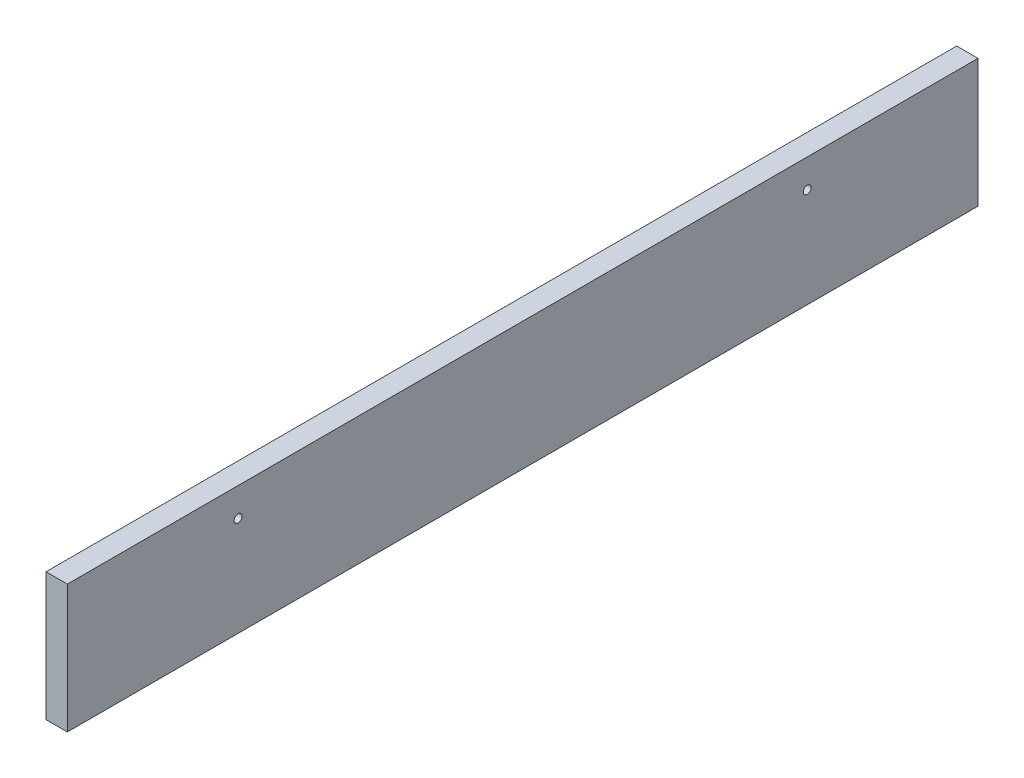
SolidWorks part; units mm, degrees
ref_plane "Front Plane" through (0, 0, 0) normal (0, 0, 1) x (1, 0, 0)
ref_plane "Top Plane" through (0, 0, 0) normal (0, 1, 0) x (1, 0, 0)
ref_plane "Right Plane" through (0, 0, 0) normal (1, 0, 0) x (0, 0, -1)
sketch "Sketch1" plane through (0, 0, 0) normal (0, 0, 1) x (1, 0, 0)
  line L1 (-6.3285, 7.7245) -> (12.7215, 7.7245)
  line L2 (-6.3285, 7.7245) -> (-6.3285, -106.5755)
  line L3 (-6.3285, -106.5755) -> (12.7215, -106.5755)
  line L4 (12.7215, 7.7245) -> (12.7215, -106.5755)
  dimension "D1" = 19.05
  dimension "D2" = 114.3
extrude "Boss-Extrude1" add sketch "Sketch1" along normal blind 812.8
ref_plane "Plane1" through (0, 0, 406.4) normal (0, 0, 1) x (1, 0, 0)
ref_plane "Plane2" through (0, -49.4255, 0) normal (0, 1, 0) x (1, 0, 0)
sketch "Sketch2" plane through (-6.3285, 0, 0) normal (-1, 0, 0) x (0, 0, 1)
  line L0 (0, 7.7245) -> (0, -106.5755) construction
  line L1 (812.8, 7.7245) -> (0, 7.7245) construction
  line L2 (812.8, 7.7245) -> (0, 7.7245) construction
  line L3 (812.8, 7.7245) -> (812.8, -106.5755) construction
  circle A0 centre (152.4, -17.6755) radius 3.556
  circle A1 centre (660.4, -17.6755) radius 3.556
  dimension "D1" = 152.4
  dimension "D3" = 25.4
  dimension "D4" = 7.112
  dimension "D5" = 7.112
  dimension "D6" = 25.4
  dimension "D2" = 152.4
extrude "Cut-Extrude3" cut sketch "Sketch2" against normal through all contours A1
extrude "Cut-Extrude4" cut sketch "Sketch2<6>" against normal through all contours A0
sketch "Sketch2<6>" plane through (-6.3285, 0, 0) normal (-1, 0, 0) x (0, 0, 1) same geometry as "Sketch2"
